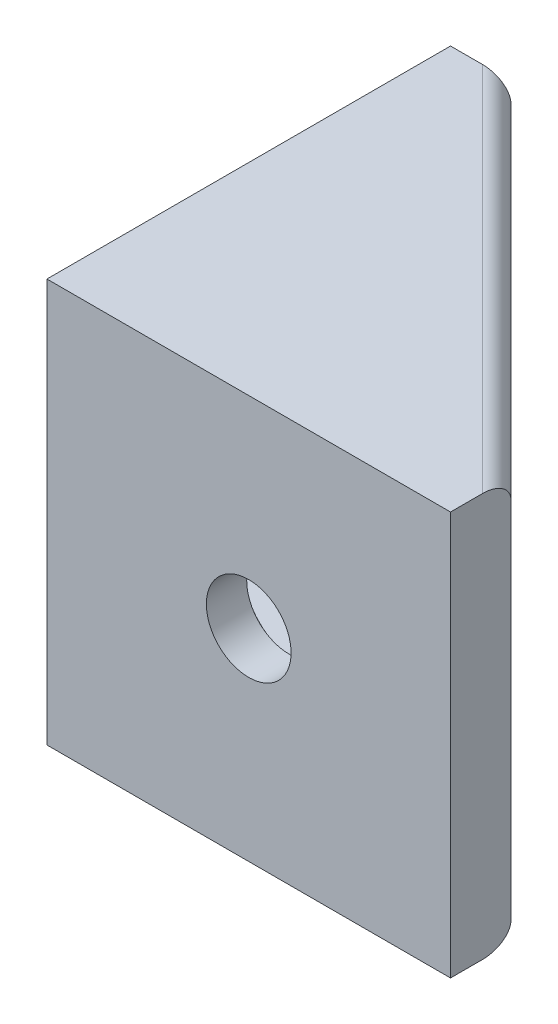
SolidWorks part; units mm, degrees
ref_plane "前视基准面" through (0, 0, 0) normal (0, 0, 1) x (1, 0, 0)
ref_plane "上视基准面" through (0, 0, 0) normal (0, 1, 0) x (1, 0, 0)
ref_plane "右视基准面" through (0, 0, 0) normal (1, 0, 0) x (0, 0, -1)
other "Configuration Table"
sketch "草图1" plane through (0, 0, 0) normal (0, 1, 0) x (1, 0, 0)
  line L0 (0, 20) -> (0, 0)
  line L1 (0, 0) -> (20, 0)
  line L2 (20, 0) -> (20, 3)
  line L3 (20, 3) -> (3, 3)
  line L4 (3, 3) -> (3, 20)
  line L5 (3, 20) -> (0, 20)
  dimension "D1" = 3
  dimension "D2" = 20
  dimension "D3" = 20
  dimension "D4" = 3
extrude "凸台-拉伸1" add sketch "草图1" along normal blind 20
sketch "草图2" plane through (0, 20, 0) normal (0, 1, 0) x (1, 0, 0)
  line L0 (3, 20) -> (20, 3)
  line L1 (20, 3) -> (3, 3)
  line L2 (3, 3) -> (3, 20)
extrude "凸台-拉伸2" add sketch "草图2" against normal blind 3
sketch "草图3" plane through (0, 0, 0) normal (0, -1, 0) x (1, 0, 0)
  line L0 (20, -3) -> (3, -20)
  line L1 (3, -20) -> (3, -3)
  line L2 (3, -3) -> (3, -20) construction
  line L3 (3, -20) -> (3, -3) construction
  line L4 (3, -3) -> (20, -3)
extrude "凸台-拉伸3" add sketch "草图3" against normal blind 3
chamfer "倒角1" distance 10 angle 45 1 edges at (3, 10, -3)
sketch "草图4" plane through (0, 0, -3) normal (0, 0, -1) x (-1, 0, 0)
  line L0 (-20, 20) -> (-3, 20) construction
  line L1 (-20, 17) -> (-20, 3) construction
  circle A0 centre (-10, 10) radius 2.1
  point P2 (0, 0)
  point P7 (-15.1759, 9.027)
  dimension "D3" = 4.2
  dimension "D1" = 10
  dimension "D2" = 10
extrude "切除-拉伸1" cut sketch "草图4" against normal blind 3
sketch "草图5" plane through (0, 0, -3) normal (0, 0, -1) x (-1, 0, 0)
  line L0 (-10, 13.5) -> (-13, 13.5)
  line L1 (-10, 6.5) -> (-13, 6.5)
  line L2 (-13, 13.5) -> (-13, 6.5)
  arc A0 (-10, 6.5) -> (-10, 13.5) centre (-10, 10) ccw
  dimension "D1" = 7
extrude "切除-拉伸2" cut sketch "草图5" along normal blind 10 contours A0 L0 L2 L1
fillet "圆角1" radius 1 2 edges at (11.5, 20, -11.5) (11.5, 0, -11.5)
sketch "草图6" plane through (3, 0, 0) normal (1, 0, 0) x (0, 0, -1)
  line L0 (1.5858, 20) -> (20, 20) construction
  line L1 (20, 17) -> (20, 3) construction
  circle A0 centre (10, 10) radius 2.1
  dimension "D3" = 4.2
  dimension "D1" = 10
  dimension "D2" = 10
extrude "切除-拉伸3" cut sketch "草图6" against normal blind 10
sketch "草图7" plane through (3, 0, 0) normal (-1, 0, 0) x (0, 0, 1)
  circle A0 centre (-10, 10) radius 3.5
  dimension "D1" = 7
extrude "切除-拉伸4" cut sketch "草图7" against normal blind 10
sketch "草图8" plane through (0, 13.5, 0) normal (0, -1, 0) x (1, 0, 0)
  line L1 (3, -13) -> (13, -13)
  line L2 (3, -13) -> (3, -3)
  line L3 (3, -3) -> (13, -3)
  line L4 (13, -13) -> (13, -3)
extrude "切除-拉伸5" cut sketch "草图8" along normal blind 7
fillet "圆角2" radius 1 4 edges at (8, 17, -8) (8, 3, -8) (8, 13.5, -8) (8, 6.5, -8)
sketch "草图9" plane through (0, 0, -3) normal (0, 0, -1) x (-1, 0, 0)
  circle A0 centre (-10, 10) radius 3.5
extrude "切除-拉伸6" cut sketch "草图9" against normal blind 1
sketch "草图10" plane through (3, 0, 0) normal (1, 0, 0) x (0, 0, -1)
  circle A0 centre (10, 10) radius 3.5
extrude "切除-拉伸7" cut sketch "草图10" against normal blind 1
